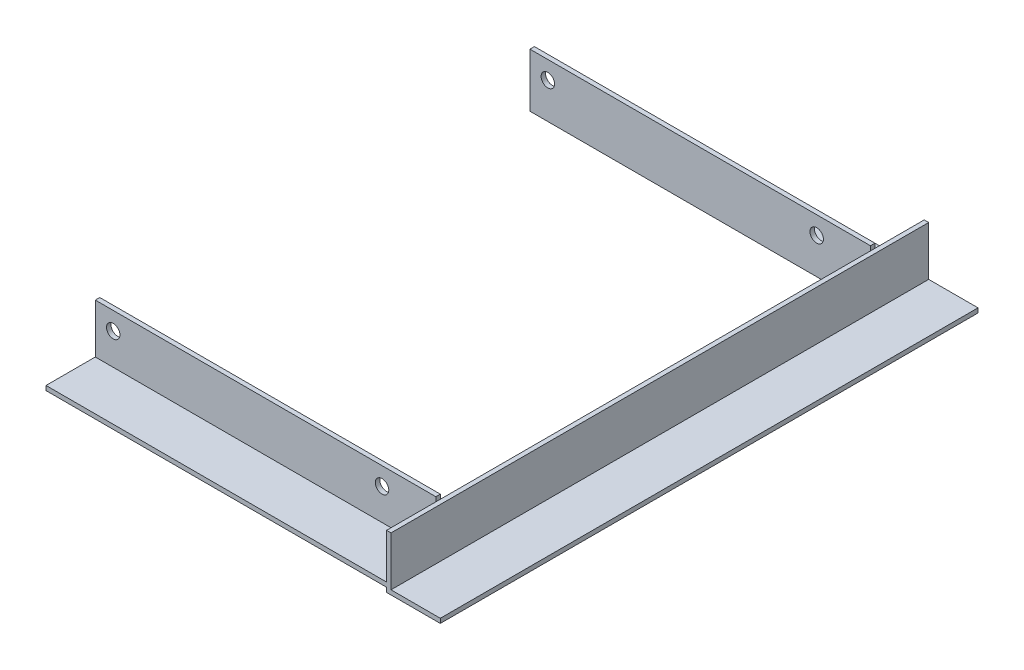
SolidWorks part; units mm, degrees
material "Plain Carbon Steel"
ref_plane "Front Plane" through (0, 0, 0) normal (0, 0, 1) x (1, 0, 0)
ref_plane "Top Plane" through (0, 0, 0) normal (0, 1, 0) x (1, 0, 0)
ref_plane "Right Plane" through (0, 0, 0) normal (1, 0, 0) x (0, 0, -1)
sketch "Sketch1" plane through (0, 0, 0) normal (0, 0, 1) x (1, 0, 0)
  line L0 (0, 0) -> (0, 38.1)
  line L1 (0, -55) -> (0, 55) construction
  line L3 (55, 0) -> (-55, 0) construction
  line L4 (38.1, 0) -> (0, 0)
  dimension "D1" = 38.1
  dimension "D2" = 38.1
extrude "Extrude-Thin1" add sketch "Sketch1" along normal mid plane 381 thin thin type one direction wall 3.175
sketch "Sketch2" plane through (0, 0, 0) normal (-1, 0, 0) x (0, 0, 1)
  line L0 (-190.5, 3.175) -> (-152.4, 3.175)
  line L2 (-152.4, 3.175) -> (-152.4, 41.275)
  line L4 (152.4, 3.175) -> (152.4, 41.275)
  line L5 (152.4, 3.175) -> (190.5, 3.175)
  line L6 (153.67, 0) -> (-153.67, 0) construction
  dimension "D1" = 152.4
  dimension "D2" = 152.4
  dimension "D3" = 3.175
  dimension "D4" = 38.1
extrude "Extrude-Thin2" add sketch "Sketch2" along normal blind 241.3 thin thin type one direction reverse wall 3.175
sketch "Sketch5" plane through (0, 0, 0) normal (0, 0, 1) x (1, 0, 0)
  line L0 (-241.3, 41.275) -> (-241.3, 6.35) construction
  line L1 (-241.3, 41.275) -> (0, 41.275) construction
  circle A0 centre (-228.6, 28.575) radius 4.7625
  circle A1 centre (-38.1, 28.575) radius 4.7625
  dimension "D1" = 9.525
  dimension "D2" = 12.7
  dimension "D3" = 12.7
  dimension "D4" = 190.5
extrude "Cut-Extrude3" cut sketch "Sketch5" against normal through all both and the other way through all
